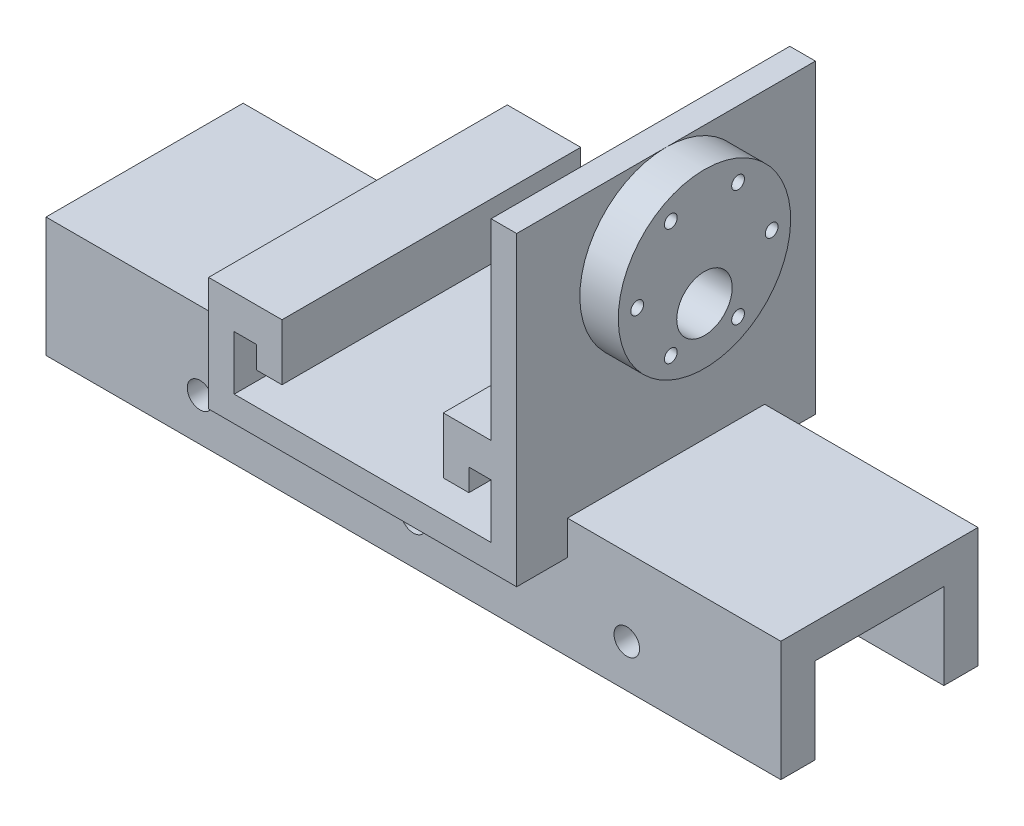
SolidWorks part; units mm, degrees
material "Nylon 101"
ref_plane "Front Plane" through (0, 0, 0) normal (0, 0, 1) x (1, 0, 0)
ref_plane "Top Plane" through (0, 0, 0) normal (0, 1, 0) x (1, 0, 0)
ref_plane "Right Plane" through (0, 0, 0) normal (1, 0, 0) x (0, 0, -1)
sketch "Sketch1" plane through (0, 0, 0) normal (0, 0, 1) x (1, 0, 0)
  line L0 (0, 26.7) -> (0, 0)
  line L1 (0, 0) -> (72.2, 0)
  line L2 (72.2, 0) -> (72.2, 71.7)
  line L3 (72.2, 71.7) -> (66.2, 71.7)
  line L4 (66.2, 71.7) -> (66.2, 26.7)
  line L5 (66.2, 6) -> (6, 6)
  line L6 (6, 6) -> (6, 18.7)
  line L7 (6, 18.7) -> (11.2, 18.7)
  line L8 (0, 26.7) -> (17.2, 26.7)
  line L10 (11.2, 18.7) -> (11.2, 13.5)
  line L11 (11.2, 13.5) -> (17.2, 13.5)
  line L12 (17.2, 13.5) -> (17.2, 26.7)
  line L13 (66.2, 26.7) -> (55, 26.7)
  line L14 (55, 26.7) -> (55, 13.5)
  line L15 (55, 13.5) -> (61, 13.5)
  line L16 (61, 13.5) -> (61, 18.7)
  line L17 (61, 18.7) -> (66.2, 18.7)
  line L18 (66.2, 18.7) -> (66.2, 6)
  dimension "D1" = 8
  dimension "D2" = 6
  dimension "D3" = 6
  dimension "D4" = 5.2
  dimension "D5" = 12.7
  dimension "D6" = 6
  dimension "D7" = 5.2
  dimension "D8" = 5.2
  dimension "D9" = 6
  dimension "D10" = 60.2
  dimension "D11" = 6
  dimension "D12" = 45
extrude "Boss-Extrude1" add sketch "Sketch1" along normal blind 70
sketch "Sketch2" plane through (66.2, 0, 0) normal (-1, 0, 0) x (0, 0, 1)
  circle A0 centre (35, 51.5) radius 15.75 construction
  circle A1 centre (50.75, 51.5) radius 1.5
  dimension "D3" = 31.5
  dimension "D2" = 51.5
  dimension "D4" = 3
  dimension "D1" = 35
extrude "Cut-Extrude1" cut sketch "Sketch2" against normal blind 6
sketch "Sketch3" plane through (0, 18.7, 0) normal (0, -1, 0) x (1, 0, 0)
  line L0 (61.1, 56) -> (66.1, 56)
  line L2 (0, 70) -> (72.2, 70) construction
  line L4 (61, 70) -> (61, 0) construction
  arc A0 (66.1, 56) -> (61.1, 56) centre (63.6, 56) ccw
  dimension "D1" = 5
  dimension "D2" = 14
  dimension "D3" = 2.6
revolve "Cut-Revolve1" cut sketch "Sketch3" angle 360 about L0
pattern_linear "LPattern1" count 4 spacing 14 along (0, 0, -1) count 2 spacing 55 along (-1, 0, 0) of "Cut-Revolve1"
sketch "Sketch4" plane through (72.2, 0, 0) normal (1, 0, 0) x (0, 0, -1)
  line L0 (-70, 0) -> (-70, 71.7) construction
  line L1 (-58.1, 8) -> (-11.9, 8)
  line L2 (-58.1, 8) -> (-58.1, 0)
  line L3 (-58.1, 0) -> (-11.9, 0)
  line L4 (-11.9, 8) -> (-11.9, 0)
  line L5 (-58.1, 8) -> (-11.9, 0) construction
  line L6 (-58.1, 0) -> (-11.9, 8) construction
  line L7 (-70, 0) -> (0, 0) construction
  point P0 (-35, 4)
  dimension "D1" = 8
  dimension "D2" = 46.2
  dimension "D3" = 11.9
extrude "Boss-Extrude2" add sketch "Sketch4" along normal blind 50
sketch "Sketch5" plane through (0, 0, 0) normal (-1, 0, 0) x (0, 0, 1)
  line L0 (70, 0) -> (0, 0) construction
  line L1 (11.9, 8) -> (58.1, 8)
  line L2 (11.9, 8) -> (11.9, 0)
  line L3 (11.9, 0) -> (58.1, 0)
  line L4 (58.1, 8) -> (58.1, 0)
  line L5 (11.9, 8) -> (58.1, 0) construction
  line L6 (11.9, 0) -> (58.1, 8) construction
  point P0 (35, 4)
  dimension "D1" = 46.2
  dimension "D2" = 8
  dimension "D3" = 11.9
extrude "Boss-Extrude3" add sketch "Sketch5" along normal blind 50
sketch "Sketch6" plane through (0, 0, 0) normal (0, -1, 0) x (1, 0, 0)
  line L1 (-50, 58.1) -> (122.2, 58.1)
  line L2 (-50, 58.1) -> (-50, 50.1)
  line L3 (-50, 50.1) -> (122.2, 50.1)
  line L4 (122.2, 58.1) -> (122.2, 50.1)
  line L5 (-50, 58.1) -> (122.2, 50.1) construction
  line L6 (-50, 50.1) -> (122.2, 58.1) construction
  line L8 (36.1, 88.663) -> (36.1, -15.4349) construction
  line L10 (-50, 11.9) -> (122.2, 11.9)
  line L11 (-50, 11.9) -> (-50, 19.9)
  line L12 (-50, 19.9) -> (122.2, 19.9)
  line L13 (122.2, 11.9) -> (122.2, 19.9)
  line L14 (-50, 11.9) -> (122.2, 19.9) construction
  line L15 (-50, 19.9) -> (122.2, 11.9) construction
  point P0 (36.1, 54.1)
  point P11 (36.1, 15.9)
  dimension "D1" = 8
  dimension "D2" = 30.2
  dimension "D3" = 11.9
  dimension "D4" = 46.2
  dimension "D5" = 172.2
  dimension "D6" = 36.1
extrude "Boss-Extrude4" add sketch "Sketch6" along normal blind 20.1
ref_plane "Plane1" through (36.1, 0, 0) normal (-1, 0, 0) x (0, 0, 1)
ref_axis "Axis1" through (66.2, 51.5, 35) along (-1, 0, 0)
pattern_circular "CirPattern2" count 6 over 360 about axis through (66.2, 51.5, 35) along (-1, 0, 0) of "Cut-Extrude1"
sketch "Sketch10" plane through (66.2, 0, 0) normal (-1, 0, 0) x (0, 0, 1)
  circle A0 centre (35, 44.5) radius 6.5
  dimension "D1" = 13
  dimension "D2" = 7
extrude "Cut-Extrude4" cut sketch "Sketch10" against normal blind 10
sketch "Sketch11" plane through (72.2, 0, 0) normal (1, 0, 0) x (0, 0, -1)
  line L0 (-70, 71.7) -> (0, 71.7) construction
  circle A0 centre (-35, 51.5) radius 20.2
  circle A1 centre (-42.875, 65.1399) radius 1.5 construction
  circle A2 centre (-27.125, 65.1399) radius 1.5 construction
  circle A3 centre (-19.25, 51.5) radius 1.5 construction
  circle A4 centre (-27.125, 37.8601) radius 1.5 construction
  circle A5 centre (-35, 44.5) radius 6.5 construction
  circle A6 centre (-42.875, 37.8601) radius 1.5 construction
  circle A7 centre (-50.75, 51.5) radius 1.5 construction
  circle A8 centre (-42.875, 65.1399) radius 1.5
  circle A9 centre (-27.125, 65.1399) radius 1.5
  circle A10 centre (-19.25, 51.5) radius 1.5
  circle A11 centre (-27.125, 37.8601) radius 1.5
  circle A12 centre (-35, 44.5) radius 6.5
  circle A13 centre (-42.875, 37.8601) radius 1.5
  circle A14 centre (-50.75, 51.5) radius 1.5
extrude "Boss-Extrude6" add sketch "Sketch11" along normal blind 9
sketch "Sketch12" plane through (0, 0, 11.9) normal (0, 0, -1) x (-1, 0, 0)
  line L0 (-36.1, -38.5) -> (-36.1, 38.5) construction
  line L1 (50, -20.1) -> (-122.2, -20.1) construction
  circle A0 centre (-36.1, -10.1) radius 3
  circle A1 centre (-86.1, -10.1) radius 3
  circle A2 centre (13.9, -10.1) radius 3
  dimension "D2" = 6
  dimension "D4" = 10
  dimension "D5" = 6
  dimension "D7" = 6
  dimension "D1" = 10
  dimension "D3" = 50
  dimension "D6" = 50
  dimension "D8" = 10
extrude "Cut-Extrude5" cut sketch "Sketch12" against normal through all
